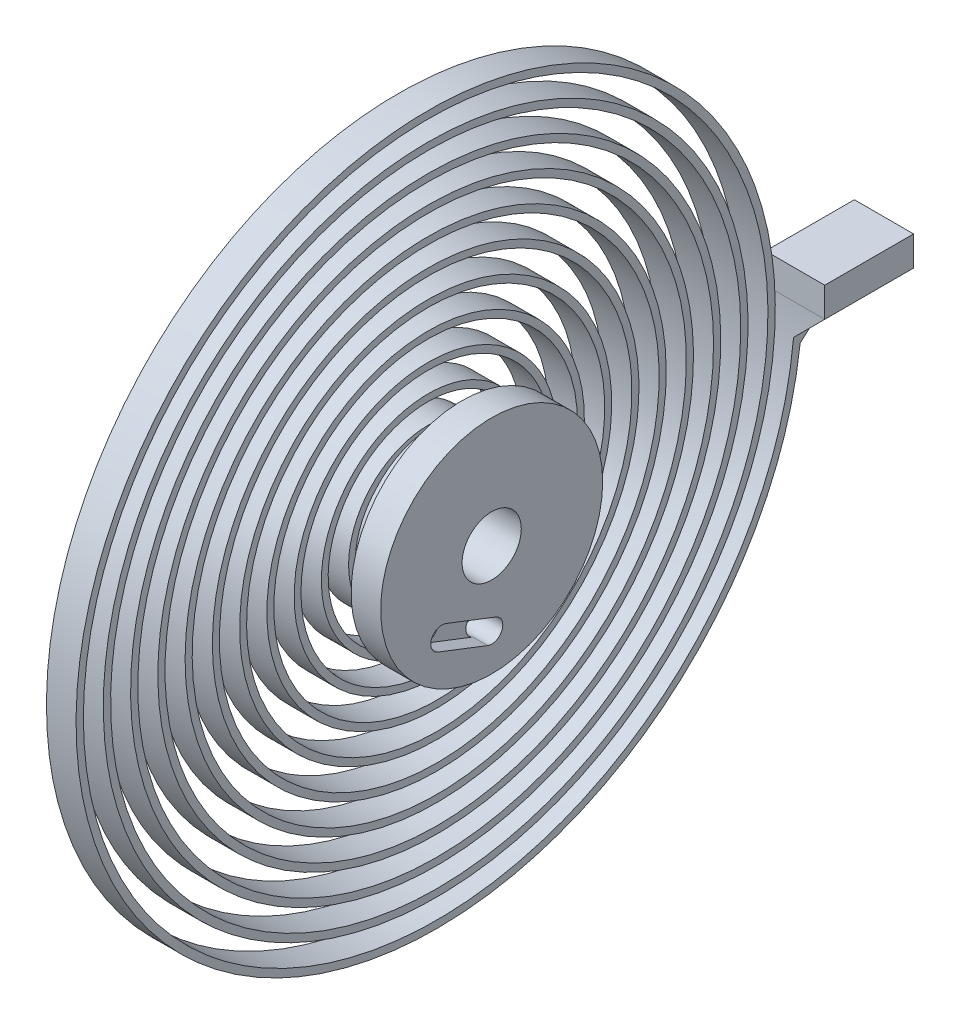
SolidWorks part; units mm, degrees
ref_plane "Front Plane" through (0, 0, 0) normal (0, 0, 1) x (1, 0, 0)
ref_plane "Top Plane" through (0, 0, 0) normal (0, 1, 0) x (1, 0, 0)
ref_plane "Right Plane" through (0, 0, 0) normal (1, 0, 0) x (0, 0, -1)
sketch "Sketch1" plane through (0, 0, 0) normal (1, 0, 0) x (0, 0, -1)
  circle A0 centre (0, 0) radius 25
  dimension "D1" = 50
curve "Helix/Spiral1"
sketch "Sketch4" plane through (0, 0, 0) normal (1, 0, 0) x (0, 0, -1)
  circle A0 centre (0, 0) radius 24.5
  circle A1 centre (0, 0) radius 25 construction
  dimension "D1" = 0.5
curve "Helix/Spiral4"
sketch "Sketch6" plane through (0, 0, 0) normal (1, 0, 0) x (0, 0, -1)
  line L0 (0.6081, 0) -> (-0.1316, 0)
  line L1 (25, 0) -> (24.5, 0)
  spline S0 degree 3 number of poles 498 (24.5, 0) -> (0.6081, 0) construction
  spline S1 degree 3 number of poles 498 (25, 0) -> (-0.1316, 0) construction
  spline S2 degree 3 number of poles 498 (24.5, 0) -> (0.6081, 0)
  spline S3 degree 3 number of poles 498 (25, 0) -> (-0.1316, 0)
extrude "Boss-Extrude2" add sketch "Sketch6" along normal blind 2 contours L0 S3 L1 S2
sketch "Sketch9" plane through (0, 0, 0) normal (0, 1, 0) x (1, 0, 0)
  line L1 (0, 24.5) -> (2, 24.5)
  line L2 (0, 24.5) -> (0, 30.5)
  line L3 (0, 30.5) -> (2, 30.5)
  line L4 (2, 24.5) -> (2, 30.5)
  dimension "D1" = 2
  dimension "D2" = 6
extrude "Boss-Extrude4" add sketch "Sketch9" along normal blind 2
sketch "Sketch12" plane through (2, 0, 0) normal (1, 0, 0) x (0, 0, -1)
  line L0 (24.5, 2) -> (24.5, 0)
  line L1 (24.5, 0) -> (24.3346, -2.5599)
  line L2 (24.8378, -2.5594) -> (27.75, 0)
  line L3 (25, 0) -> (30.5, 0) construction
  line L4 (27.75, 0) -> (27.75, 2)
  line L5 (24.5, 2) -> (30.5, 2) construction
  line L6 (27.75, 2) -> (24.5, 2)
  line L7 (24.5, 2) -> (17.0027, 2.0052)
  arc A0 (24.3346, -2.5599) -> (24.8378, -2.5594) centre (24.5825, 1.277) ccw
  spline S0 degree 3 number of poles 498 (24.5, 0) -> (0.6081, 0) construction
  spline S1 degree 3 number of poles 498 (25, 0) -> (-0.1316, 0) construction
  spline M1 degree 3 poles (24.5, 0) (24.4689, -2.6057) (24.0186, -5.2009) (22.331, -10.111) (21.094, -12.425) (17.9633, -16.5419) (16.07, -18.3441) (11.8221, -21.2597) (9.4682, -22.3727) (4.5391, -23.8029) (1.9648, -24.12) (-3.1444, -23.9323) (-5.6783, -23.4277) (-10.452, -21.6535) (-12.691, -20.3844) (-16.6515, -17.2146) (-18.3725, -15.3145) (-21.1279, -11.0788) (-22.1618, -8.744) (-23.4442, -3.8769) (-23.6924, -1.3456) (-23.3843, 3.6583) (-22.828, 6.1299) (-20.973, 10.766) (-19.6746, 12.9297) (-16.4715, 16.7346) (-14.5674, 18.3751) (-10.3493, 20.9726) (-8.0359, 21.9291) (-3.2351, 23.0675) (-0.7485, 23.2493) (4.1472, 22.8257) (6.5556, 22.2206) (11.053, 20.2903) (13.1414, 18.9656) (16.7914, 15.7349) (18.3524, 13.8296) (20.7945, 9.6341) (21.6753, 7.3447) (22.6738, 2.6143) (22.7914, 0.1741) (22.2576, -4.611) (21.6063, -6.9552) (19.6065, -11.3132) (18.2583, -13.3263) (15.0057, -16.8224) (13.1019, -18.3047) (8.9341, -20.5942) (6.6708, -21.401) (2.0147, -22.2638) (-0.3774, -22.3196) (-5.0495, -21.6806) (-7.3287, -20.9861) (-11.5466, -18.9223) (-13.4846, -17.5535) (-16.8278, -14.2846) (-18.2326, -12.385) (-20.3723, -8.2498) (-21.107, -6.0149) (-21.8383, -1.4368) (-21.8347, 0.9057) (-21.0959, 5.4625) (-20.3608, 7.676) (-18.2388, 11.7533) (-16.8523, 13.6164) (-13.5724, 16.8083) (-11.6797, 18.1365) (-7.5819, 20.1295) (-5.3776, 20.794) (-0.881, 21.3981) (1.4104, 21.3377) (5.8499, 20.5042) (7.9972, 19.7313) (11.9337, 17.5567) (13.7222, 16.1553) (16.7641, 12.87) (18.0171, 10.9867) (19.8665, 6.9309) (20.4626, 4.7592) (20.944, 0.3478) (20.8293, -1.8912) (19.9065, -6.2116) (19.0986, -8.2922) (16.877, -12.0877) (15.4636, -13.8021) (12.1781, -16.6958) (10.3067, -17.8748) (6.2976, -19.5839) (4.1605, -20.1137) (-0.1627, -20.477) (-2.348, -20.3104) (-6.5476, -19.3036) (-8.5611, -18.4636) (-12.2158, -16.2005) (-13.8565, -14.7778) (-16.6039, -11.4975) (-17.7102, -9.6405) (-19.2824, -5.6823) (-19.7481, -3.5818) (-19.9978, 0.65) (-19.782, 2.7805) (-18.6965, 6.8578) (-17.8272, 8.8039) (-15.5281, 12.3181) (-14.0989, 13.8857) (-10.8289, 16.4889) (-8.9887, 17.524) (-5.0858, 18.9628) (-3.0236, 19.3664) (1.1139, 19.5073) (3.1885, 19.2448) (7.1423, 18.0861) (9.0207, 17.1902) (12.395, 14.8607) (13.8902, 13.4277) (16.3512, 10.173) (17.3166, 8.352) (18.6258, 4.5084) (18.9695, 2.4864) (19.0064, -1.5541) (18.6998, -3.5719) (17.4732, -7.4011) (16.5535, -9.2118) (14.1991, -12.4467) (12.7649, -13.8703) (9.5306, -16.1916) (7.7311, -17.0889) (3.9507, -18.2722) (1.9705, -18.5581) (-1.9705, -18.4959) (-3.9305, -18.1478) (-7.6341, -16.8588) (-9.3771, -15.9181) (-12.4736, -13.5442) (-13.8265, -12.1114) (-16.0105, -8.9022) (-16.8413, -7.1264) (-17.9027, -3.4131) (-18.1332, -1.4763) (-17.9767, 2.3627) (-17.5898, 4.2642) (-16.2437, 7.8416) (-15.2848, 9.517) (-12.8966, 12.476) (-11.4679, 13.7591) (-8.2886, 15.8086) (-6.5387, 16.5746) (-2.8961, 17.5181) (-1.0041, 17.6954) (2.7307, 17.4497) (4.573, 17.0267) (8.0237, 15.6289) (9.6316, 14.6544) (12.4543, 12.2573) (13.6687, 10.8352) (15.5865, 7.6904) (16.2895, 5.9684) (17.1192, 2.4001) (17.2457, 0.5544) (16.9157, -3.0743) (16.4592, -4.8567) (15.0151, -8.1804) (14.0279, -9.7211) (11.6271, -12.409) (10.214, -13.5558) (7.1083, -15.3447) (5.4162, -15.9867) (1.9254, -16.7068) (0.1273, -16.7849) (-3.3934, -16.3756) (-5.1154, -15.8883) (-8.3119, -14.4034) (-9.7858, -13.406) (-12.3405, -11.0066) (-13.4208, -9.6051) (-15.0841, -6.5427) (-15.6668, -4.8825) (-16.2816, -1.4724) (-16.3138, 0.2767) (-15.8303, 3.6878) (-15.3149, 5.3492) (-13.7944, 8.4185) (-12.7896, 9.826) (-10.3967, 12.2491) (-9.0091, 13.2643) (-5.9944, 14.8052) (-4.3679, 15.3306) (-1.0416, 15.8446) (0.6576, 15.8332) (3.9577, 15.2808) (5.5579, 14.7399) (8.5004, 13.1892) (9.8421, 12.1795) (12.1356, 9.7981) (13.0869, 8.4267) (14.5087, 5.4638) (14.9789, 3.8728) (15.3965, 0.633) (15.344, -1.0151) (14.7278, -4.2028) (14.1642, -5.7418) (12.5884, -8.5578) (11.5766, -9.8343) (9.2115, -12.0002) (7.8586, -12.8892) (4.9514, -14.1954) (3.3976, -14.6123) (0.2471, -14.9382) (-1.349, -14.8471) (-4.4233, -14.1722) (-5.9009, -13.5885) (-8.5909, -11.9931) (-9.803, -10.9816) (-11.8435, -8.6376) (-12.6717, -7.3055) (-13.8659, -4.4578) (-14.2318, -2.9428) (-14.4705, 0.1159) (-14.3434, 1.6592) (-13.6149, 4.6191) (-13.0138, 6.0352) (-11.4039, 8.6002) (-10.3954, 9.7486) (-8.0772, 11.6662) (-6.7679, 12.435) (-3.9835, 13.521) (-2.5089, 13.838) (0.4558, 13.9943) (1.9454, 13.8336) (4.7903, 13.0569) (6.1451, 12.441) (8.5859, 10.8217) (9.6716, 9.8186) (11.4687, 7.5308) (12.1799, 6.2464) (13.1615, 3.5288) (13.4318, 2.096) (13.5104, -0.7725) (13.3187, -2.2077) (12.4989, -4.937) (11.8709, -6.2305) (10.2473, -8.5484) (9.2521, -9.5723) (6.9991, -11.2516) (5.7417, -11.9068) (3.0943, -12.788) (1.7047, -13.0139) (-1.0656, -13.0197) (-2.4459, -12.7996) (-5.0593, -11.9418) (-6.2919, -11.3043) (-8.488, -9.6815) (-9.4512, -8.6966) (-11.0156, -6.4827) (-11.6166, -5.2542) (-12.4014, -2.6803) (-12.5852, -1.3352) (-12.5229, 1.3352) (-12.2771, 2.6601) (-11.3866, 5.1573) (-10.7421, 6.3293) (-9.125, 8.4052) (-8.1527, 9.3089) (-5.9823, 10.7613) (-4.7846, 11.31) (-2.2871, 12.0025) (-0.9878, 12.1464) (1.5811, 12.0211) (2.8501, 11.752) (5.2313, 10.8339) (6.343, 10.1852) (8.3004, 8.5787) (9.1457, 7.6213) (10.4893, 5.4984) (10.9875, 4.3333) (11.5921, 1.9153) (11.6985, 0.6627) (11.5151, -1.8031) (11.2253, -3.016) (10.2848, -5.2813) (9.6342, -6.3334) (8.0432, -8.174) (7.103, -8.9623) (5.0316, -10.2003) (3.9009, -10.6499) (1.565, -11.1709) (0.3603, -11.2422) (-2.0014, -11.0056) (-3.1579, -10.6978) (-5.3077, -9.7399) (-6.3007, -9.0901) (-8.0266, -7.5192) (-8.7592, -6.5984) (-9.895, -4.5824) (-10.298, -3.4877) (-10.7397, -1.2365) (-10.7784, -0.0806) (-10.4937, 2.1757) (-10.1703, 3.2757) (-9.2002, 5.3107) (-8.5537, 6.2453) (-7.0075, 7.8586) (-6.1083, 8.5369) (-4.1514, 9.574) (-3.0942, 9.9325) (-0.9302, 10.2995) (0.1761, 10.3079) (2.3262, 9.9801) (3.3697, 9.6438) (5.2905, 8.6665) (6.1675, 8.0257) (7.6705, 6.5088) (8.2961, 5.6332) (9.238, 3.739) (9.5542, 2.7208) (9.851, 0.6463) (9.8316, -0.4096) (9.4657, -2.4529) (9.1191, -3.4399) (8.1396, -5.2474) (7.5068, -6.0678) (6.0238, -7.4628) (5.1738, -8.0374) (3.3457, -8.8879) (2.3679, -9.1638) (0.385, -9.395) (-0.6199, -9.3504) (-2.5558, -8.9513) (-3.4864, -8.597) (-5.1819, -7.6202) (-5.9464, -6.9979) (-7.2362, -5.553) (-7.7613, -4.7306) (-8.5243, -2.9719) (-8.7621, -2.036) (-8.9324, -0.1464) (-8.865, 0.8068) (-8.4379, 2.6349) (-8.0784, 3.5095) (-7.1092, 5.0941) (-6.4997, 5.8039) (-5.0971, 6.9912) (-4.3042, 7.4686) (-2.6181, 8.1479) (-1.7252, 8.3499) (0.0692, 8.4641) (0.9703, 8.3763) (2.6906, 7.9263) (3.5094, 7.5641) (4.9846, 6.6073) (5.6408, 6.013) (6.7285, 4.6568) (7.1598, 3.8952) (7.7596, 2.2846) (7.928, 1.4359) (7.9908, -0.2617) (7.8853, -1.1103) (7.4173, -2.7227) (7.0549, -3.4862) (6.1153, -4.8537) (5.5383, -5.4574) (4.2326, -6.4485) (3.5041, -6.8357) (1.9719, -7.3601) (1.1685, -7.4972) (-0.431, -7.5134) (-1.2269, -7.3927) (-2.7317, -6.9117) (-3.4403, -6.5516) (-4.7018, -5.6339) (-5.2543, -5.0765) (-6.152, -3.8251) (-6.497, -3.1313) (-6.9502, -1.6802) (-7.0583, -0.9231) (-7.0329, 0.5771) (-6.8994, 1.32) (-6.4105, 2.7175) (-6.0551, 3.372) (-5.1639, 4.5293) (-4.6282, 5.0321) (-3.4349, 5.8397) (-2.7774, 6.1444) (-1.4098, 6.5307) (-0.6999, 6.6122) (0.6999, 6.55) (1.3897, 6.4063) (2.6805, 5.9143) (3.2814, 5.5662) (4.3369, 4.7059) (4.7912, 4.194) (5.5121, 3.0624) (5.7786, 2.4429) (6.1024, 1.1612) (6.1597, 0.4993) (6.0655, -0.7994) (5.9142, -1.436) (5.4241, -2.6209) (5.0856, -3.1691) (4.2607, -4.1248) (3.7747, -4.5323) (2.7082, -5.1701) (2.128, -5.4003) (0.9345, -5.666) (0.3213, -5.7015) (-0.8756, -5.5805) (-1.4591, -5.4239) (-2.539, -4.9407) (-3.0353, -4.614) (-3.8938, -3.829) (-4.2559, -3.3707) (-4.8142, -2.3728) (-5.0103, -1.8333) (-5.2226, -0.7299) (-5.2387, -0.1661) (-5.0956, 0.9284) (-4.9364, 1.459) (-4.4647, 2.4351) (-4.1524, 2.8804) (-3.4114, 3.6442) (-2.9828, 3.9626) (-2.0566, 4.4452) (-1.5591, 4.6094) (-0.5477, 4.7727) (-0.0339, 4.7719) (0.9581, 4.6117) (1.436, 4.4524) (2.3094, 3.9971) (2.7048, 3.7014) (3.3767, 3.0085) (3.653, 2.6115) (4.0638, 1.7601) (4.1982, 1.3058) (4.3174, 0.388) (4.3021, -0.0754) (4.1298, -0.9646) (3.9727, -1.3902) (3.5386, -2.1624) (3.2617, -2.509) (2.621, -3.0918) (2.2573, -3.3279) (1.4836, -3.6709) (1.0737, -3.7777) (0.2511, -3.8573) (-0.1616, -3.8301) (-0.9481, -3.6505) (-1.3218, -3.4983) (-1.9945, -3.09) (-2.2934, -2.8341) (-2.7901, -2.2494) (-2.9878, -1.9208) (-3.2671, -1.2276) (-3.3486, -0.8631) (-3.3935, -0.137) (-3.3567, 0.2247) (-3.1749, 0.9087) (-3.0299, 1.231) (-2.652, 1.806) (-2.4192, 2.0585) (-1.8945, 2.4723) (-1.6025, 2.6334) (-0.9924, 2.8531) (-0.6743, 2.9118) (-0.0458, 2.9266) (0.2646, 2.8829) (0.8466, 2.7036) (1.1182, 2.5683) (1.5973, 2.2253) (1.8049, 2.0178) (2.1389, 1.5566) (2.2654, 1.303) (2.4299, 0.7784) (2.4679, 0.5075) (2.4576, -0.0224) (2.4093, -0.2815) (2.2376, -0.7621) (2.1143, -0.9835) (1.8107, -1.369) (1.6306, -1.5329) (1.2364, -1.7907) (1.0225, -1.8846) (0.3674, -2.055) (-0.0853, -2.0166) (-0.8452, -1.698) (-1.1507, -1.4199) (-1.5209, -0.7726) (-1.5856, -0.4062) (-1.4935, 0.2549) (-1.3382, 0.5476) (-0.9146, 0.9577) (-0.6484, 1.0747) (-0.1386, 1.1249) (0.1032, 1.0593) (0.4666, 0.819) (0.5876, 0.6463) (0.6891, 0.3006) (0.6703, 0.1294) (0.6081, 0) knots 0 0 0 0 0.003906 0.003906 0.007812 0.007812 0.011719 0.011719 0.015625 0.015625 0.019531 0.019531 0.023437 0.023437 0.027344 0.027344 0.03125 0.03125 0.035156 0.035156 0.039062 0.039062 0.042969 0.042969 0.046875 0.046875 0.050781 0.050781 0.054687 0.054687 0.058594 0.058594 0.0625 0.0625 0.066406 0.066406 0.070312 0.070312 0.074219 0.074219 0.078125 0.078125 0.082031 0.082031 0.085937 0.085937 0.089844 0.089844 0.09375 0.09375 0.097656 0.097656 0.101562 0.101562 0.105469 0.105469 0.109375 0.109375 0.113281 0.113281 0.117187 0.117187 0.121094 0.121094 0.125 0.125 0.128906 0.128906 0.132812 0.132812 0.136719 0.136719 0.140625 0.140625 0.144531 0.144531 0.148437 0.148437 0.152344 0.152344 0.15625 0.15625 0.160156 0.160156 0.164062 0.164062 0.167969 0.167969 0.171875 0.171875 0.175781 0.175781 0.179687 0.179687 0.183594 0.183594 0.1875 0.1875 0.191406 0.191406 0.195312 0.195312 0.199219 0.199219 0.203125 0.203125 0.207031 0.207031 0.210937 0.210937 0.214844 0.214844 0.21875 0.21875 0.222656 0.222656 0.226562 0.226562 0.230469 0.230469 0.234375 0.234375 0.238281 0.238281 0.242187 0.242187 0.246094 0.246094 0.25 0.25 0.253906 0.253906 0.257812 0.257812 0.261719 0.261719 0.265625 0.265625 0.269531 0.269531 0.273437 0.273437 0.277344 0.277344 0.28125 0.28125 0.285156 0.285156 0.289062 0.289062 0.292969 0.292969 0.296875 0.296875 0.300781 0.300781 0.304687 0.304687 0.308594 0.308594 0.3125 0.3125 0.316406 0.316406 0.320312 0.320312 0.324219 0.324219 0.328125 0.328125 0.332031 0.332031 0.335937 0.335937 0.339844 0.339844 0.34375 0.34375 0.347656 0.347656 0.351562 0.351562 0.355469 0.355469 0.359375 0.359375 0.363281 0.363281 0.367187 0.367187 0.371094 0.371094 0.375 0.375 0.378906 0.378906 0.382812 0.382812 0.386719 0.386719 0.390625 0.390625 0.394531 0.394531 0.398437 0.398437 0.402344 0.402344 0.40625 0.40625 0.410156 0.410156 0.414062 0.414062 0.417969 0.417969 0.421875 0.421875 0.425781 0.425781 0.429687 0.429687 0.433594 0.433594 0.4375 0.4375 0.441406 0.441406 0.445312 0.445312 0.449219 0.449219 0.453125 0.453125 0.457031 0.457031 0.460937 0.460937 0.464844 0.464844 0.46875 0.46875 0.472656 0.472656 0.476562 0.476562 0.480469 0.480469 0.484375 0.484375 0.488281 0.488281 0.492187 0.492187 0.496094 0.496094 0.5 0.5 0.503906 0.503906 0.507812 0.507812 0.511719 0.511719 0.515625 0.515625 0.519531 0.519531 0.523437 0.523437 0.527344 0.527344 0.53125 0.53125 0.535156 0.535156 0.539062 0.539062 0.542969 0.542969 0.546875 0.546875 0.550781 0.550781 0.554687 0.554687 0.558594 0.558594 0.5625 0.5625 0.566406 0.566406 0.570312 0.570312 0.574219 0.574219 0.578125 0.578125 0.582031 0.582031 0.585937 0.585937 0.589844 0.589844 0.59375 0.59375 0.597656 0.597656 0.601562 0.601562 0.605469 0.605469 0.609375 0.609375 0.613281 0.613281 0.617187 0.617187 0.621094 0.621094 0.625 0.625 0.628906 0.628906 0.632812 0.632812 0.636719 0.636719 0.640625 0.640625 0.644531 0.644531 0.648437 0.648437 0.652344 0.652344 0.65625 0.65625 0.660156 0.660156 0.664062 0.664062 0.667969 0.667969 0.671875 0.671875 0.675781 0.675781 0.679687 0.679687 0.683594 0.683594 0.6875 0.6875 0.691406 0.691406 0.695312 0.695312 0.699219 0.699219 0.703125 0.703125 0.707031 0.707031 0.710937 0.710937 0.714844 0.714844 0.71875 0.71875 0.722656 0.722656 0.726562 0.726562 0.730469 0.730469 0.734375 0.734375 0.738281 0.738281 0.742187 0.742187 0.746094 0.746094 0.75 0.75 0.753906 0.753906 0.757812 0.757812 0.761719 0.761719 0.765625 0.765625 0.769531 0.769531 0.773437 0.773437 0.777344 0.777344 0.78125 0.78125 0.785156 0.785156 0.789062 0.789062 0.792969 0.792969 0.796875 0.796875 0.800781 0.800781 0.804687 0.804687 0.808594 0.808594 0.8125 0.8125 0.816406 0.816406 0.820312 0.820312 0.824219 0.824219 0.828125 0.828125 0.832031 0.832031 0.835937 0.835937 0.839844 0.839844 0.84375 0.84375 0.847656 0.847656 0.851562 0.851562 0.855469 0.855469 0.859375 0.859375 0.863281 0.863281 0.867187 0.867187 0.871094 0.871094 0.875 0.875 0.878906 0.878906 0.882812 0.882812 0.886719 0.886719 0.890625 0.890625 0.894531 0.894531 0.898437 0.898437 0.902344 0.902344 0.90625 0.90625 0.910156 0.910156 0.914062 0.914062 0.917969 0.917969 0.921875 0.921875 0.925781 0.925781 0.929687 0.929687 0.933594 0.933594 0.9375 0.9375 0.945312 0.945312 0.953125 0.953125 0.960937 0.960937 0.96875 0.96875 0.976562 0.976562 0.984375 0.984375 0.992187 0.992187 1 1 1 1
  spline M3 degree 3 poles (-0.1316, 0) (-0.1963, -0.0291) (-0.2501, -0.1039) (-0.2637, -0.2971) (-0.2221, -0.4138) (-0.0307, -0.5953) (0.119, -0.6579) (0.46, -0.6484) (0.6497, -0.5749) (0.9532, -0.2819) (1.0646, -0.0626) (1.1089, 0.4397) (1.04, 0.7208) (0.7024, 1.2017) (0.4335, 1.3987) (-0.2141, 1.5764) (-0.591, 1.5548) (-1.1094, 1.3252) (-1.274, 1.2167) (-1.564, 0.9425) (-1.6894, 0.7768) (-1.8811, 0.4027) (-1.9474, 0.1945) (-2.0068, -0.243) (-1.9999, -0.4722) (-1.9065, -0.9255) (-1.82, -1.1494) (-1.5708, -1.5644) (-1.4081, -1.7553) (-1.0194, -2.0781) (-0.7934, -2.21) (-0.2999, -2.3937) (-0.0325, -2.4456) (0.5153, -2.4567) (0.7956, -2.4159) (1.3367, -2.2393) (1.5974, -2.1034) (2.0672, -1.7456) (2.2761, -1.5236) (2.6138, -1.0134) (2.7425, -0.7252) (2.8989, -0.1116) (2.9267, 0.2136) (2.8711, 0.8658) (2.7878, 1.1926) (2.5125, 1.81) (2.3206, 2.1003) (1.8434, 2.6087) (1.5582, 2.8266) (0.9217, 3.1604) (0.5706, 3.2761) (-0.1613, 3.3859) (-0.5418, 3.38) (-1.2902, 3.24) (-1.658, 3.106) (-2.3379, 2.7181) (-2.6498, 2.4642) (-3.1794, 1.859) (-3.3967, 1.5077) (-3.707, 0.7427) (-3.7998, 0.3291) (-3.8438, -0.5167) (-3.795, -0.9487) (-3.554, -1.783) (-3.3618, -2.185) (-2.8489, -2.9121) (-2.5283, -3.2369) (-1.7885, -3.7688) (-1.3695, -3.9757) (-0.476, -4.2427) (-0.0016, -4.3027) (0.9515, -4.2622) (1.43, -4.1616) (2.3375, -3.8041) (2.7662, -3.5471) (3.5233, -2.8988) (3.8516, -2.5075) (4.3663, -1.629) (4.5526, -1.1419) (4.7564, -0.1224) (4.7738, 0.4097) (4.6307, 1.461) (4.4702, 1.98) (3.9821, 2.9462) (3.6545, 3.3931) (2.8624, 4.1619) (2.398, 4.4836) (1.3789, 4.9609) (0.8245, 5.1163) (-0.3158, 5.2372) (-0.9015, 5.2025) (-2.0397, 4.9399) (-2.5921, 4.7119) (-3.6005, 4.0809) (-4.0563, 3.678) (-4.8172, 2.7358) (-5.122, 2.1968) (-5.5413, 1.0379) (-5.6555, 0.4182) (-5.6742, -0.8355) (-5.5785, -1.4693) (-5.1805, -2.6809) (-4.8783, -3.2584) (-4.094, -4.2911) (-3.6121, -4.746) (-2.5161, -5.4784) (-1.9023, -5.7557) (-0.6067, -6.0962) (0.0748, -6.1592) (1.4319, -6.057) (2.1073, -5.8918) (3.3767, -5.3444) (3.9705, -4.9621) (5.0079, -4.0163) (5.4513, -3.4528) (6.1341, -2.2017) (6.3732, -1.5142) (6.6144, -0.0877) (6.6163, 0.6511) (6.3759, 2.0994) (6.1335, 2.8088) (5.424, 4.1185) (4.9569, 4.7187) (3.8435, 5.7402) (3.1972, 6.1613) (1.792, 6.7728) (1.0333, 6.963) (-0.5159, 7.0848) (-1.306, 7.0165) (-2.8311, 6.6215) (-3.5657, 6.295) (-4.8967, 5.4128) (-5.4928, 4.8573) (-6.4768, 3.5726) (-6.8645, 2.8436) (-7.383, 1.2881) (-7.5137, 0.4618) (-7.497, -1.1992) (-7.3494, -2.0337) (-6.7853, -3.6189) (-6.3687, -4.3693) (-5.3055, -5.7009) (-4.6591, -6.2819) (-3.202, -7.2061) (-2.3916, -7.5491) (-0.692, -7.9532) (0.1968, -8.0142) (1.9566, -7.8405) (2.8272, -7.6058) (4.454, -6.8595) (5.2097, -6.3479) (6.5202, -5.0976) (7.0746, -4.3591) (7.9163, -2.7311) (8.2033, -1.8419) (8.4719, -0.0073) (8.4534, 0.9377) (8.1059, 2.7808) (7.7769, 3.6785) (6.8374, 5.3266) (6.2271, 6.0766) (4.7861, 7.343) (3.9555, 7.8591) (2.1608, 8.5954) (1.1968, 8.8153) (-0.7613, 8.9281) (-1.7551, 8.821) (-3.6638, 8.2842) (-4.5784, 7.8547) (-6.226, 6.7134) (-6.9586, 6.0018) (-8.1574, 4.369) (-8.6233, 3.4479) (-9.2315, 1.4932) (-9.3736, 0.4599) (-9.3114, -1.6078) (-9.1072, -2.6417) (-8.3675, -4.5965) (-7.8323, -5.517) (-6.4828, -7.1409) (-5.6688, -7.8441) (-3.8457, -8.9513) (-2.837, -9.3551) (-0.7318, -9.8129) (0.3643, -9.8668) (2.5251, -9.6117) (3.5894, -9.3028) (5.5688, -8.3487) (6.4834, -7.7038) (8.0596, -6.1423) (8.7208, -5.2259) (9.7121, -3.217) (10.0421, -2.1249) (10.3281, 0.1186) (10.2841, 1.2695) (9.8198, 3.5049) (9.3995, 4.5889) (8.2218, 6.5697) (7.4646, 7.4662) (5.6897, 8.9696) (4.6725, 9.5762) (2.485, 10.4277) (1.3151, 10.6724) (-1.052, 10.7662) (-2.2486, 10.6153) (-4.5378, 9.9272) (-5.6298, 9.3902) (-7.5877, 7.9819) (-8.4531, 7.1109) (-9.8583, 5.1244) (-10.3978, 4.0094) (-11.0858, 1.6531) (-11.2342, 0.4123) (-11.1167, -2.061) (-10.8508, -3.2931) (-9.9266, -5.6134) (-9.2685, -6.7011) (-7.6253, -8.6105) (-6.6406, -9.4317) (-4.4469, -10.713) (-3.2384, -11.1728) (-0.726, -11.6745) (0.5773, -11.7162) (3.1373, -11.3699) (4.3936, -10.9819) (6.7207, -9.8115) (7.791, -9.0292) (9.6254, -7.1497) (10.389, -6.0528) (11.5208, -3.6592) (11.8888, -2.3629) (12.1823, 0.2901) (12.1077, 1.6463) (11.5169, 4.2713) (11.0008, 5.5395) (9.5765, 7.8475) (8.6686, 8.8869) (6.5541, 10.6192) (5.3479, 11.3118) (2.7645, 12.2691) (1.3878, 12.5334) (-1.3878, 12.5982) (-2.7863, 12.3985) (-5.4524, 11.5498) (-6.7195, 10.9009) (-8.9813, 9.2178) (-9.9757, 8.184) (-11.5788, 5.8387) (-12.1871, 4.5277) (-12.9452, 1.7676) (-13.0948, 0.3192) (-12.912, -2.5587) (-12.5795, -3.9876) (-11.4617, -6.6691) (-10.6765, -7.9212) (-8.7326, -10.109) (-7.5742, -11.0442) (-5.0054, -12.4907) (-3.5955, -13.0016) (-0.6746, -13.5372) (0.8357, -13.5616) (3.793, -13.1142) (5.2394, -12.6424) (7.9091, -11.2469) (9.1319, -10.3235) (11.2168, -8.1195) (12.0786, -6.8394) (13.3416, -4.0573) (13.7426, -2.5559) (14.0335, 0.5071) (13.9233, 2.0681) (13.1964, 5.0799) (12.5799, 6.53) (10.9009, 9.1594) (9.8387, 10.338) (7.3786, 12.2911) (5.9812, 13.0652) (2.9991, 14.1185) (1.4151, 14.3976) (-1.7688, 14.4233) (-3.3681, 14.1699) (-6.4075, 13.1512) (-7.8469, 12.386) (-10.4062, 10.4206) (-11.5257, 9.2207) (-13.3179, 6.5114) (-13.9904, 5.0026) (-14.8088, 1.8368) (-14.9545, 0.1804) (-14.6964, -3.1008) (-14.2926, -4.725) (-12.9722, -7.7632) (-12.0558, -9.1767) (-9.8041, -11.6357) (-8.4691, -12.6807) (-5.5208, -14.2833) (-3.9081, -14.8406) (-0.5777, -15.4001) (1.1395, -15.4022) (4.4919, -14.8439) (6.1265, -14.2835) (9.1337, -12.6545) (10.5055, -11.586) (12.8334, -9.0512) (13.7888, -7.5853) (15.1736, -4.4113) (15.6027, -2.7038) (15.8809, 0.7695) (15.73, 2.5346) (14.8576, 5.9302) (14.1361, 7.56) (12.1943, 10.5047) (10.9743, 11.819) (8.163, 13.9847) (6.5721, 14.8356) (3.1887, 15.9754) (1.3968, 16.264) (-2.1948, 16.2406) (-3.9938, 15.9285) (-7.4025, 14.7306) (-9.0116, 13.8448) (-11.8618, 11.5895) (-13.1024, 10.2203) (-15.0751, 7.1422) (-15.8069, 5.4338) (-16.6757, 1.8604) (-16.8125, -0.0039) (-16.4693, -3.6869) (-15.9892, -5.5049) (-14.4573, -8.8952) (-13.4057, -10.467) (-10.8392, -13.19) (-9.3248, -14.3407) (-5.9929, -16.0903) (-4.1761, -16.6889) (-0.435, -17.2624) (1.4885, -17.237) (5.2337, -16.5581) (7.0546, -15.9046) (10.3938, -14.0334) (11.9114, -12.8161) (14.4742, -9.9442) (15.5189, -8.2902) (17.016, -4.7208) (17.4682, -2.8063) (17.7238, 1.0774) (17.5272, 3.0457) (16.4996, 6.8219) (15.6687, 8.629) (13.4561, 11.883) (12.0749, 13.3292) (8.9068, 15.6991) (7.1204, 16.6222) (3.3332, 17.8387) (1.3329, 18.1319) (-2.6656, 18.0494) (-4.663, 17.6737) (-8.4372, 16.2873) (-10.2132, 15.2767) (-13.3474, 12.7241) (-14.7051, 11.1825) (-16.8496, 7.7307) (-17.6359, 5.8211) (-18.5452, 1.8385) (-18.668, -0.2339) (-18.2296, -4.317) (-17.6685, -6.327) (-15.9163, -10.0647) (-14.7255, -11.7917) (-11.8375, -14.7713) (-10.1408, -16.0233) (-6.4213, -17.9107) (-4.3992, -18.5458) (-0.2468, -19.1232) (1.8828, -19.0654) (6.0182, -18.2561) (8.0233, -17.5047) (11.6889, -15.3831) (13.3488, -14.0133) (16.1387, -10.7982) (17.2681, -8.9535) (18.8681, -4.9857) (19.3382, -2.8633) (19.5612, 1.4306) (19.3139, 3.6013) (18.1217, 7.7547) (17.1769, 9.7366) (14.6857, 13.2937) (13.1399, 14.8681) (9.6095, 17.4336) (7.6258, 18.4242) (3.4323, 19.7077) (1.2234, 20.0003) (-3.181, 19.8488) (-5.3756, 19.4046) (-9.5111, 17.8206) (-11.4511, 16.681) (-14.8625, 13.8238) (-16.3332, 12.1067) (-18.6404, 8.2766) (-19.4764, 6.1643) (-20.4164, 1.7709) (-20.5201, -0.5093) (-19.9768, -4.9908) (-19.3298, -7.1911) (-17.3486, -11.2712) (-16.0146, -13.1502) (-12.7984, -16.3789) (-10.9169, -17.7279) (-6.8059, -19.7438) (-4.5774, -20.4103) (-0.0129, -20.9817) (2.3221, -20.8864) (6.8451, -19.9371) (9.0322, -19.0832) (13.0186, -16.7029) (14.8171, -15.1769) (17.826, -11.6127) (19.0357, -9.5751) (20.7289, -5.2058) (21.212, -2.8749) (21.3923, 1.829) (21.0893, 4.2011) (19.7231, 8.7282) (18.66, 10.8824) (15.8825, 14.7361) (14.1687, 16.4348) (10.271, 19.1875) (8.0878, 20.2409) (3.486, 21.5816) (1.0681, 21.8686) (-3.741, 21.638) (-6.1313, 21.1204) (-10.6237, 19.3297) (-12.7248, 18.0569) (-16.4064, 14.888) (-17.986, 12.9925) (-20.447, 8.7796) (-21.3278, 6.4631) (-22.2884, 1.6576) (-22.3679, -0.8303) (-21.7098, -5.708) (-20.9723, -8.0969) (-18.7534, -12.5142) (-17.2723, -14.5419) (-13.7215, -18.012) (-11.6524, -19.4537) (-7.1464, -21.5888) (-4.7103, -22.2818) (0.2665, -22.8371) (2.8064, -22.6992) (7.714, -21.6002) (10.0809, -20.6394) (14.3823, -17.9922) (16.3159, -16.3064) (19.5356, -12.3872) (20.8209, -10.1545) (22.5977, -5.3809) (23.0888, -2.8409) (23.2163, 2.2726) (22.8527, 4.845) (21.3031, 9.7421) (20.1174, 12.0659) (17.046, 16.2097) (15.1608, 18.0288) (10.8906, 20.96) (8.5064, 22.0714) (3.4942, 23.4594) (0.8672, 23.7357) (-4.3453, 23.4162) (-6.9299, 22.8203) (-11.7746, 20.814) (-14.0339, 19.4039) (-17.9784, 15.9162) (-19.6628, 13.8393) (-22.2685, 9.2394) (-23.1892, 6.7172) (-24.1604, 1.4987) (-24.2107, -1.1967) (-23.428, -6.4685) (-22.5952, -9.0439) (-20.1301, -13.7933) (-18.4981, -15.9663) (-14.6063, -19.67) (-12.3471, -21.1999) (-7.4425, -23.4448) (-4.798, -24.1593) (0.5915, -24.6885) (3.3354, -24.5029) (8.6247, -23.2448) (11.169, -22.1724) (15.7794, -19.2503) (17.8444, -17.4012) (21.2666, -13.1213) (22.623, -10.6915) (24.4737, -5.5109) (24.9676, -2.7612) (25, 0) knots 0 0 0 0 0.007813 0.007813 0.015625 0.015625 0.023438 0.023438 0.03125 0.03125 0.039063 0.039063 0.046875 0.046875 0.054688 0.054688 0.0625 0.0625 0.066406 0.066406 0.070313 0.070313 0.074219 0.074219 0.078125 0.078125 0.082031 0.082031 0.085938 0.085938 0.089844 0.089844 0.09375 0.09375 0.097656 0.097656 0.101563 0.101563 0.105469 0.105469 0.109375 0.109375 0.113281 0.113281 0.117188 0.117188 0.121094 0.121094 0.125 0.125 0.128906 0.128906 0.132813 0.132813 0.136719 0.136719 0.140625 0.140625 0.144531 0.144531 0.148438 0.148438 0.152344 0.152344 0.15625 0.15625 0.160156 0.160156 0.164063 0.164063 0.167969 0.167969 0.171875 0.171875 0.175781 0.175781 0.179688 0.179688 0.183594 0.183594 0.1875 0.1875 0.191406 0.191406 0.195313 0.195313 0.199219 0.199219 0.203125 0.203125 0.207031 0.207031 0.210938 0.210938 0.214844 0.214844 0.21875 0.21875 0.222656 0.222656 0.226563 0.226563 0.230469 0.230469 0.234375 0.234375 0.238281 0.238281 0.242188 0.242188 0.246094 0.246094 0.25 0.25 0.253906 0.253906 0.257813 0.257813 0.261719 0.261719 0.265625 0.265625 0.269531 0.269531 0.273438 0.273438 0.277344 0.277344 0.28125 0.28125 0.285156 0.285156 0.289063 0.289063 0.292969 0.292969 0.296875 0.296875 0.300781 0.300781 0.304688 0.304688 0.308594 0.308594 0.3125 0.3125 0.316406 0.316406 0.320313 0.320313 0.324219 0.324219 0.328125 0.328125 0.332031 0.332031 0.335938 0.335938 0.339844 0.339844 0.34375 0.34375 0.347656 0.347656 0.351563 0.351563 0.355469 0.355469 0.359375 0.359375 0.363281 0.363281 0.367188 0.367188 0.371094 0.371094 0.375 0.375 0.378906 0.378906 0.382813 0.382813 0.386719 0.386719 0.390625 0.390625 0.394531 0.394531 0.398438 0.398438 0.402344 0.402344 0.40625 0.40625 0.410156 0.410156 0.414063 0.414063 0.417969 0.417969 0.421875 0.421875 0.425781 0.425781 0.429688 0.429688 0.433594 0.433594 0.4375 0.4375 0.441406 0.441406 0.445313 0.445313 0.449219 0.449219 0.453125 0.453125 0.457031 0.457031 0.460938 0.460938 0.464844 0.464844 0.46875 0.46875 0.472656 0.472656 0.476563 0.476563 0.480469 0.480469 0.484375 0.484375 0.488281 0.488281 0.492188 0.492188 0.496094 0.496094 0.5 0.5 0.503906 0.503906 0.507813 0.507813 0.511719 0.511719 0.515625 0.515625 0.519531 0.519531 0.523438 0.523438 0.527344 0.527344 0.53125 0.53125 0.535156 0.535156 0.539063 0.539063 0.542969 0.542969 0.546875 0.546875 0.550781 0.550781 0.554688 0.554688 0.558594 0.558594 0.5625 0.5625 0.566406 0.566406 0.570313 0.570313 0.574219 0.574219 0.578125 0.578125 0.582031 0.582031 0.585938 0.585938 0.589844 0.589844 0.59375 0.59375 0.597656 0.597656 0.601563 0.601563 0.605469 0.605469 0.609375 0.609375 0.613281 0.613281 0.617188 0.617188 0.621094 0.621094 0.625 0.625 0.628906 0.628906 0.632813 0.632813 0.636719 0.636719 0.640625 0.640625 0.644531 0.644531 0.648438 0.648438 0.652344 0.652344 0.65625 0.65625 0.660156 0.660156 0.664063 0.664063 0.667969 0.667969 0.671875 0.671875 0.675781 0.675781 0.679688 0.679688 0.683594 0.683594 0.6875 0.6875 0.691406 0.691406 0.695313 0.695313 0.699219 0.699219 0.703125 0.703125 0.707031 0.707031 0.710938 0.710938 0.714844 0.714844 0.71875 0.71875 0.722656 0.722656 0.726563 0.726563 0.730469 0.730469 0.734375 0.734375 0.738281 0.738281 0.742188 0.742188 0.746094 0.746094 0.75 0.75 0.753906 0.753906 0.757813 0.757813 0.761719 0.761719 0.765625 0.765625 0.769531 0.769531 0.773438 0.773438 0.777344 0.777344 0.78125 0.78125 0.785156 0.785156 0.789063 0.789063 0.792969 0.792969 0.796875 0.796875 0.800781 0.800781 0.804688 0.804688 0.808594 0.808594 0.8125 0.8125 0.816406 0.816406 0.820313 0.820313 0.824219 0.824219 0.828125 0.828125 0.832031 0.832031 0.835938 0.835938 0.839844 0.839844 0.84375 0.84375 0.847656 0.847656 0.851563 0.851563 0.855469 0.855469 0.859375 0.859375 0.863281 0.863281 0.867188 0.867188 0.871094 0.871094 0.875 0.875 0.878906 0.878906 0.882813 0.882813 0.886719 0.886719 0.890625 0.890625 0.894531 0.894531 0.898438 0.898438 0.902344 0.902344 0.90625 0.90625 0.910156 0.910156 0.914063 0.914063 0.917969 0.917969 0.921875 0.921875 0.925781 0.925781 0.929688 0.929688 0.933594 0.933594 0.9375 0.9375 0.941406 0.941406 0.945313 0.945313 0.949219 0.949219 0.953125 0.953125 0.957031 0.957031 0.960938 0.960938 0.964844 0.964844 0.96875 0.96875 0.972656 0.972656 0.976563 0.976563 0.980469 0.980469 0.984375 0.984375 0.988281 0.988281 0.992188 0.992188 0.996094 0.996094 1 1 1 1
  line M4 (25, 0) -> (30.5, 0)
  line M6 (30.5, 2) -> (24.5, 2)
  line M7 (24.5, 2) -> (24.5, 0)
extrude "Boss-Extrude6" add sketch "Sketch12" against normal blind 2 contours A0 L4 M1 M3 M4 M6 M7 | L2 M3 M4 region at (2, 0.6229, -25.8881) region at (2, -0.8462, -25.8778)
sketch "Sketch14" plane through (2, 0, 0) normal (1, 0, 0) x (0, 0, -1)
  circle A0 centre (0, 0) radius 5
  dimension "D1" = 10
extrude "Boss-Extrude9" add sketch "Sketch14" against normal up to surface (2 mm away) and the other way blind 4 up to face at (0, 0.0201, -23.4369)
sketch "Sketch15" plane through (6, 0, 0) normal (1, 0, 0) x (0, 0, -1)
  circle A0 centre (0, 0) radius 7.5
  dimension "D1" = 15
extrude "Boss-Extrude10" add sketch "Sketch15" against normal blind 2
sketch "Sketch16" plane through (6, 0, 0) normal (1, 0, 0) x (0, 0, -1)
  circle A0 centre (0, 0) radius 2
  dimension "D1" = 4
extrude "Cut-Extrude1" cut sketch "Sketch16" against normal up to surface (6 mm away) up to face at (0, -0.6016, -23.471)
sketch "Sketch17" plane through (4, 0, 0) normal (-1, 0, 0) x (0, 0, 1)
  circle A0 centre (0, -5) radius 0.75
  circle A1 centre (0, 0) radius 5 construction
  dimension "D1" = 1.5
extrude "Cut-Extrude2" cut sketch "Sketch17" along normal blind 2 and the other way up to surface (2 mm away) other way up to face at (6, 0, -2)
sketch "Sketch18" plane through (2, 0, 0) normal (1, 0, 0) x (0, 0, -1)
  line L0 (30.5, 2) -> (30.5, 0) construction
  line L1 (24.5, 2) -> (30.5, 2)
  line L2 (24.5, 2) -> (24.5, 0)
  line L3 (24.5, 0) -> (30.5, 0)
  line L4 (30.5, 2) -> (30.5, 0)
  line L5 (27.75, 0) -> (30.5, 0) construction
extrude "Boss-Extrude11" add sketch "Sketch18" along normal blind 2
chamfer "Chamfer1" distance 2 angle 45 1 edges at (2, 0, -26.125)
sketch "Sketch19" plane through (4, 0, 0) normal (-1, 0, 0) x (0, 0, 1)
  circle A0 centre (3.3667, -3.6966) radius 0.75
  arc A1 (0.7479, -4.9438) -> (-0.7479, -4.9438) centre (0, 0) ccw construction
  dimension "D1" = 1.5
extrude "Cut-Extrude3" cut sketch "Sketch19" against normal blind 2 and the other way blind 2
sketch "Sketch20" plane through (6, 0, 0) normal (1, 0, 0) x (0, 0, -1)
  line L0 (-3.3667, -3.6966) -> (0, -5) construction
  line L1 (-3.096, -2.9972) -> (0.2708, -4.3006)
  line L2 (-3.6375, -4.396) -> (-0.2708, -5.6994)
  arc A0 (-3.096, -2.9972) -> (-3.6375, -4.396) centre (-3.3667, -3.6966) ccw
  arc A1 (-0.2708, -5.6994) -> (0.2708, -4.3006) centre (0, -5) ccw
  circle A2 centre (0, -5) radius 0.75 construction
  circle A3 centre (-3.3667, -3.6966) radius 0.75 construction
  point P2 (-1.6834, -4.3483)
extrude "Cut-Extrude4" cut sketch "Sketch20" against normal blind 1
